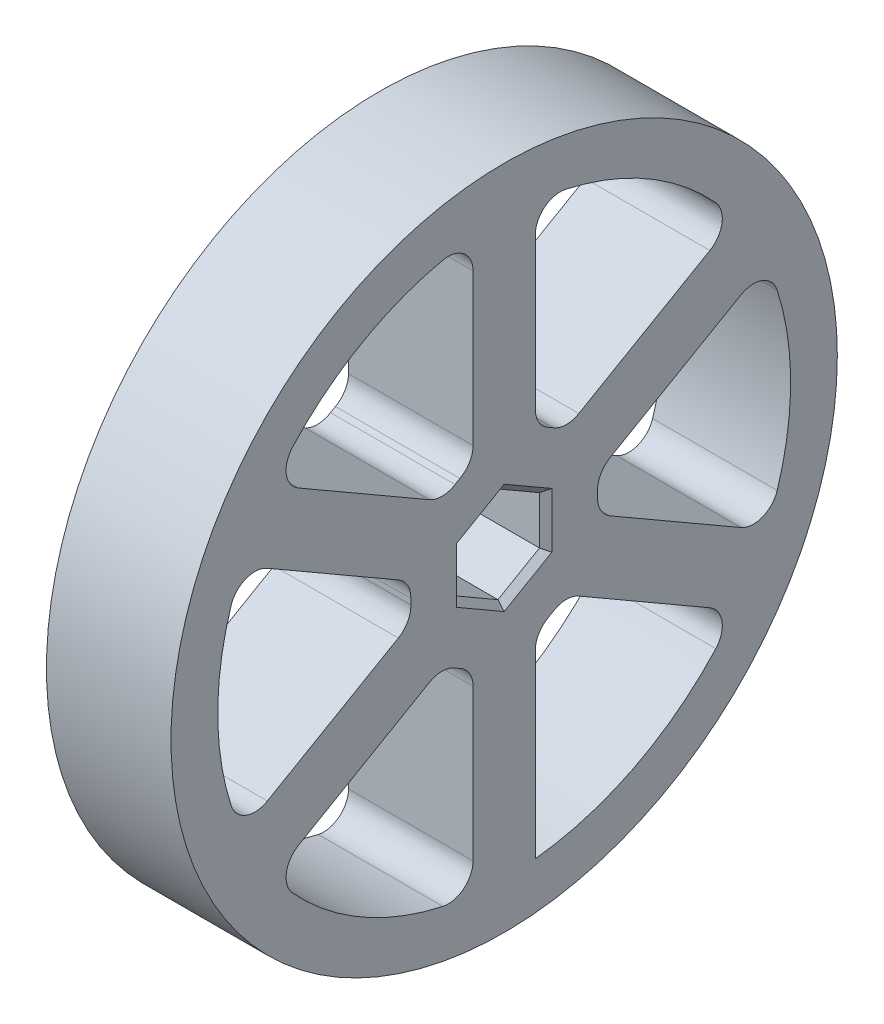
SolidWorks part; units mm, degrees
ref_plane "Front Plane" through (0, 0, 0) normal (0, 0, 1) x (1, 0, 0)
ref_plane "Top Plane" through (0, 0, 0) normal (0, 1, 0) x (1, 0, 0)
ref_plane "Right Plane" through (0, 0, 0) normal (1, 0, 0) x (0, 0, -1)
sketch "Axle Profile" plane through (0, 0, 0) normal (1, 0, 0) x (0, 0, -1)
  line L1 (0, -4.8895) -> (4.2344, -2.4448)
  line L2 (4.2344, -2.4448) -> (4.2344, 2.4447)
  line L3 (4.2344, 2.4447) -> (0, 4.8895)
  line L4 (0, 4.8895) -> (-4.2344, 2.4448)
  line L5 (-4.2344, 2.4448) -> (-4.2344, -2.4448)
  line L6 (-4.2344, -2.4448) -> (0, -4.8895)
  circle A0 centre (0, 0) radius 4.8895 construction
  circle A1 centre (0, 0) radius 9.525
  dimension "D1" = 9.779
  dimension ".625" = 19.05
extrude "Wheel Hub" add sketch "Axle Profile" along normal blind 12.7
fillet "Hub Fillet" [suppressed] radius 2.032
ref_plane "Spoke Plane" through (0, 0, -4.2344) normal (0, 0, 1) x (1, 0, 0)
sketch "Sketch2" plane through (0, 0, -4.2344) normal (0, 0, 1) x (1, 0, 0)
  line L0 (12.7, 2.4448) -> (0, -2.4447) construction
  line L1 (0, 2.4448) -> (12.7, -2.4447) construction
  circle A0 centre (6.35, 0) radius 2.54
  dimension "D1" = 5.08
extrude "Spoke" [suppressed] add sketch "Sketch2" against normal blind 25.4
ref_axis "Pattern Axis" through (12.7, 0, 0) along (-1, 0, 0)
pattern_circular "CirPattern1" [suppressed] count 6 over 360 about axis through (12.7, 0, 0) along (-1, 0, 0) of bodies 102
fillet "Hub/Spoke Fillet" [suppressed] radius 2.54
ref_plane "Mid Plane" through (6.35, 0, 0) normal (-1, 0, 0) x (0, 0, 1)
sketch "Sketch3" plane through (6.35, 0, 0) normal (-1, 0, 0) x (0, 0, 1)
  circle A0 centre (0, 0) radius 29.21
  circle A1 centre (0, 0) radius 33.9725
  dimension "D1" = 58.42
  dimension "D2" = 67.945
extrude "Wheel Rim" add sketch "Sketch3" along normal up to surface and the other way up to surface up to face at (0, 0, -9.525) other way up to face at (12.7, 0, -9.525)
fillet "Rim/Spoke Fillet" [suppressed] radius 2.54
fillet "Rim Fillet" [suppressed] radius 0.762
sketch "Sketch4" plane through (12.7, 0, 0) normal (1, 0, 0) x (0, 0, -1)
  line L0 (0, 8.9803) -> (0, 0) construction
  line L1 (-3.175, 8.9803) -> (3.175, 8.9803)
  line L2 (-3.175, 8.9803) -> (-3.175, 29.21)
  line L3 (-3.175, 29.21) -> (3.175, 29.21)
  line L4 (3.175, 8.9803) -> (3.175, 29.21)
  circle A0 centre (0, 0) radius 9.525 construction
  circle A1 centre (0, 0) radius 29.21 construction
  dimension "D1" = 6.35
extrude "Boss-Extrude1" add sketch "Sketch4" against normal up to surface (12.7 mm away) up to face at (0, 0, -29.21)
pattern_circular "Spokes" count 6 over 360 about axis through (0, 0, 0) along (1, 0, 0) of "Boss-Extrude1"
fillet "Spoke Fillets" radius 2.54 23 edges at (6.35, 8.9803, 3.175) (6.35, 7.2398, 6.1896) (6.35, -1.7405, 9.3646) (6.35, 1.7405, 9.3646) (6.35, -8.9803, 3.175) (6.35, -7.2398, 6.1896) (6.35, -8.9803, -3.175) (6.35, -7.2398, -6.1896) (6.35, -1.7405, -9.3646) (6.35, 1.7405, -9.3646) (6.35, 7.2398, -6.1896) (6.35, 8.9803, -3.175) (6.35, 29.0369, -3.175) (6.35, 29.0369, 3.175) (6.35, 17.2681, 23.5592) (6.35, 11.7688, 26.7342) (6.35, -11.7688, 26.7342) (6.35, -17.2681, 23.5592) (6.35, -29.0369, 3.175) (6.35, -17.2681, -23.5592) (6.35, -11.7688, -26.7342) (6.35, 11.7688, -26.7342) (6.35, 17.2681, -23.5592)
chamfer "Shaft Chamfers" distance 0.635 angle 45 12 edges at (0, 0, 4.2344) (0, 3.6671, 2.1172) (0, 3.6671, -2.1172) (0, 0, -4.2344) (0, -3.6671, -2.1172) (0, -3.6671, 2.1172) (12.7, -3.6671, -2.1172) (12.7, -3.6671, 2.1172) (12.7, 0, 4.2344) (12.7, 3.6671, 2.1172) (12.7, 3.6671, -2.1172) (12.7, 0, -4.2344)
